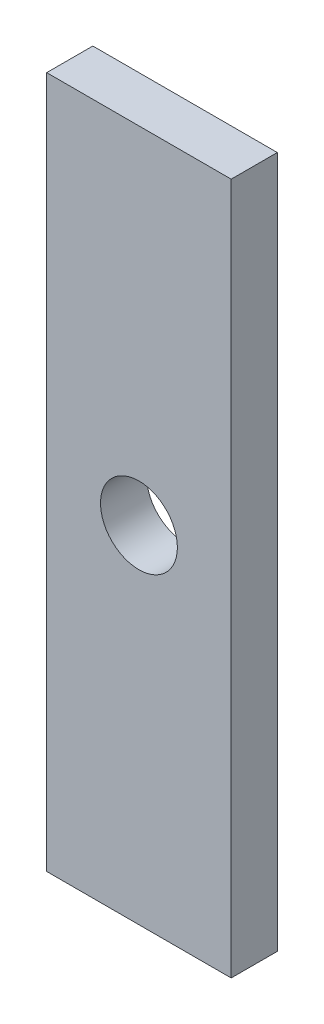
SolidWorks part; units mm, degrees
ref_plane "Front Plane" through (0, 0, 0) normal (1, 0, 0) x (0, 1, 0)
ref_plane "Top Plane" through (0, 0, 0) normal (0, 0, 1) x (0, 1, 0)
ref_plane "Right Plane" through (0, 0, 0) normal (0, 1, 0) x (-1, 0, 0)
sketch "Sketch1" plane through (0, 0, 0) normal (0, 0, 1) x (0, 1, 0)
  line L1 (-22.5, -6) -> (22.5, -6)
  line L2 (-22.5, -6) -> (-22.5, 6)
  line L3 (-22.5, 6) -> (22.5, 6)
  line L4 (22.5, -6) -> (22.5, 6)
  line L5 (-22.5, -6) -> (22.5, 6) construction
  line L6 (-22.5, 6) -> (22.5, -6) construction
  circle A0 centre (0, 0) radius 2.5
  point P0 (0, 0)
  dimension "D1" = 5
  dimension "D2" = 45
  dimension "D3" = 12
extrude "Boss-Extrude1" add sketch "Sketch1" along normal blind 3
